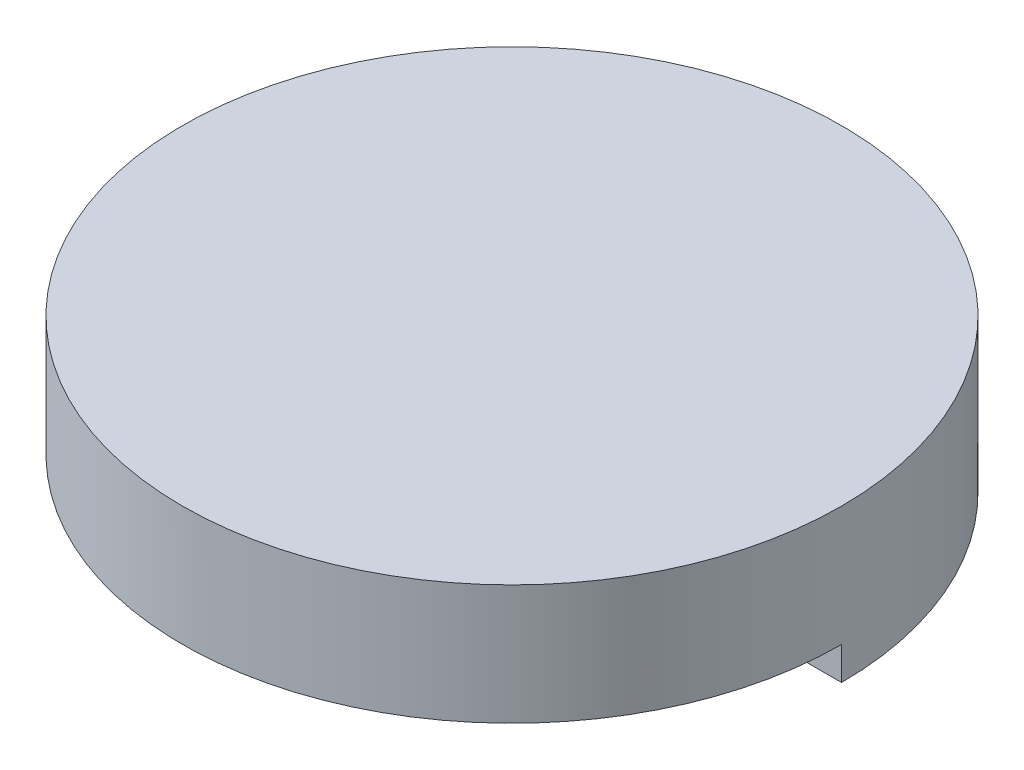
SolidWorks part; units mm, degrees
ref_plane "Front Plane" through (0, 0, 0) normal (0, 0, 1) x (1, 0, 0)
ref_plane "Top Plane" through (0, 0, 0) normal (0, 1, 0) x (1, 0, 0)
ref_plane "Right Plane" through (0, 0, 0) normal (1, 0, 0) x (0, 0, -1)
sketch "Sketch2" plane through (0, 0, 0) normal (0, 1, 0) x (1, 0, 0)
  circle A0 centre (0, 0) radius 11
  dimension "D1" = 22
extrude "Boss-Extrude1" add sketch "Sketch2" along normal blind 4
sketch "Sketch3" plane through (0, 0, 0) normal (0, 1, 0) x (1, 0, 0)
  line L0 (-10, 0) -> (-11, 0)
  line L1 (10, 0) -> (11, 0)
  arc A0 (-11, 0) -> (11, 0) centre (0, 0) cw
  circle A1 centre (0, 0) radius 11 construction
  arc A3 (-10, 0) -> (10, 0) centre (0, 0) cw
  dimension "D1" = 1
extrude "Boss-Extrude2" add sketch "Sketch3" against normal blind 0.6
sketch "Sketch4" plane through (0, -0.6, 0) normal (0, -1, 0) x (1, 0, 0)
  line L0 (-11, 0) -> (-8.5, 0)
  line L1 (8.5, 0) -> (11, 0)
  arc A0 (-11, 0) -> (11, 0) centre (0, 0) ccw
  arc A2 (-8.5, 0) -> (8.5, 0) centre (0, 0) ccw
  dimension "D1" = 2.5
extrude "Boss-Extrude3" add sketch "Sketch4" along normal blind 0.5
